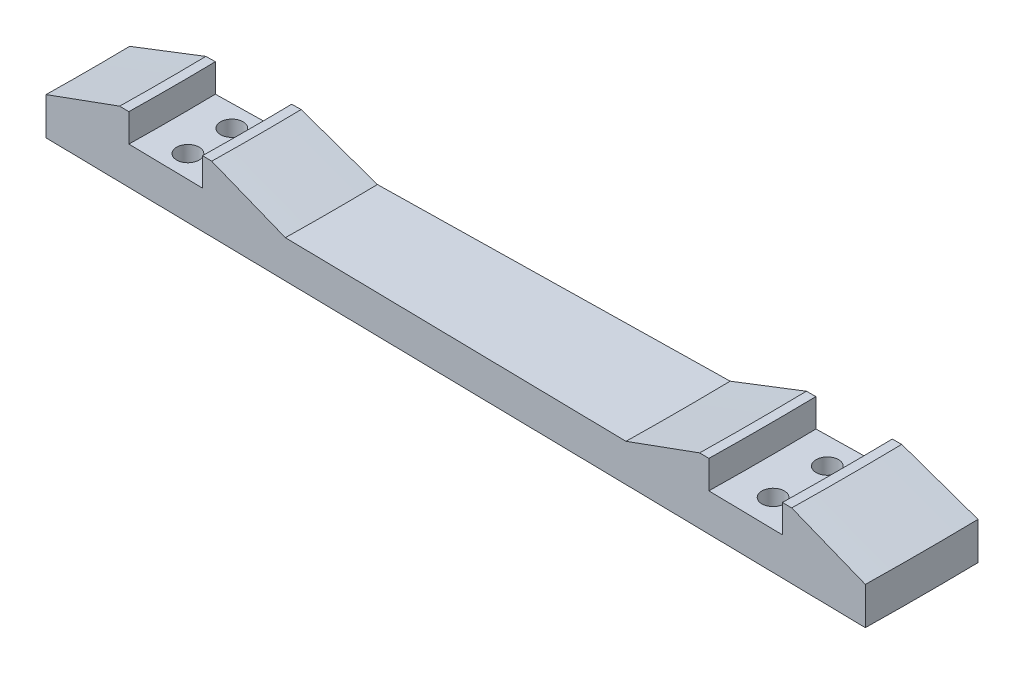
SolidWorks part; units mm, degrees
other "标注1"
sketch "草图3" plane through (-22.25, 4, -10) normal (-0.231, 0.6469, -0.7268) x (-0.9696, -0.2151, 0.1167)
ref_plane "前视基准面" through (0, 0, 0) normal (0, 0, 1) x (1, 0, 0)
ref_plane "上视基准面" through (0, 0, 0) normal (0, 1, 0) x (1, 0, 0)
ref_plane "右视基准面" through (0, 0, 0) normal (1, 0, 0) x (0, 0, -1)
other "Configuration Table"
sketch "草图4" plane through (0, 0, 0) normal (0, 0, 1) x (1, 0, 0)
  line L6 (8.5, -1.5) -> (17.75, -1.5)
  line L11 (17.75, -1.5) -> (17.75, -3.5)
  line L16 (17.75, -3.5) -> (-4.5, -3.5)
  line L17 (-4.5, -3.5) -> (-4.5, -1.5)
  line L19 (0, 0) -> (0, -1.5)
  line L20 (0, -1.5) -> (4, -1.5)
  line L21 (4, -1.5) -> (4, 0)
  line L26 (4, 0) -> (4.5, 0)
  line L27 (4.5, 0) -> (8.5, -1.5)
  line L28 (0, 0) -> (-0.5, 0)
  line L29 (-0.5, 0) -> (-4.5, -1.5)
  dimension "D2" = 4
  dimension "D4" = 0.5
  dimension "D5" = 2
  dimension "D6" = 2
  dimension "D7" = 4
  dimension "D8" = 1.5
  dimension "D9" = 4
  dimension "D10" = 22.25
extrude "凸台-拉伸1" add sketch "草图4" along normal blind 2.5 contours L28 L29 L17 L16 L11 L6 L27 L26 L21 L20 L19 | L19 | L21 region at (5.9579, -2.2764, 0)
sketch "草图5" plane through (0, -1.5, 0) normal (0, 1, 0) x (1, 0, 0)
  line L0 (0, 0) -> (4, -2.5) construction
  line L1 (0, -2.5) -> (0, 0) construction
  line L2 (0, -2.5) -> (4, -2.5) construction
  line L3 (4, -2.5) -> (4, 0) construction
  line L4 (0, 0) -> (4, 0) construction
  circle A0 centre (2, -1.25) radius 0.6
  circle A1 centre (2, -1.25) radius 1
  dimension "D1" = 1.2
  dimension "D2" = 2
extrude "切除-拉伸1" cut sketch "草图5" against normal through all contours A0
extrude "切除-拉伸2" cut sketch "草图5<3>" along normal blind 1 from surface contours A1 starting at face at (2, -3.5, 1.85)
sketch "草图5<3>" plane through (0, -1.5, 0) normal (0, 1, 0) x (1, 0, 0) same geometry as "草图5"
mirror "镜向1" about plane through (17.75, 0, 2.5) normal (1, 0, 0) of bodies 215
sketch "草图6" plane through (0, 0, 2.5) normal (0, 0, 1) x (1, 0, 0)
  line L18 (0, 0) -> (-0.5, 0)
  line L19 (-0.5, 0) -> (-4.5, -1.5)
  line L20 (-4.5, -1.5) -> (-4.5, -3.5)
  line L21 (-4.5, -3.5) -> (40, -3.5)
  line L22 (40, -3.5) -> (40, -1.5)
  line L23 (40, -1.5) -> (36, 0)
  line L24 (36, 0) -> (35.5, 0)
  line L25 (35.5, 0) -> (35.5, -1.5)
  line L26 (35.5, -1.5) -> (31.5, -1.5)
  line L27 (31.5, -1.5) -> (31.5, 0)
  line L28 (31.5, 0) -> (31, 0)
  line L29 (31, 0) -> (27, -1.5)
  line L30 (27, -1.5) -> (8.5, -1.5)
  line L31 (8.5, -1.5) -> (4.5, 0)
  line L32 (4.5, 0) -> (4, 0)
  line L33 (4, 0) -> (4, -1.5)
  line L34 (4, -1.5) -> (0, -1.5)
  line L35 (0, -1.5) -> (0, 0)
  line L36 (0, 0) -> (-0.5, 0)
  line L37 (-0.5, 0) -> (-4.5, -1.5)
  line L38 (-4.5, -1.5) -> (-4.5, -3.5)
  line L39 (-4.5, -3.5) -> (40, -3.5)
  line L40 (40, -3.5) -> (40, -1.5)
  line L41 (40, -1.5) -> (36, 0)
  line L42 (36, 0) -> (35.5, 0)
  line L43 (35.5, 0) -> (35.5, -1.5)
  line L44 (35.5, -1.5) -> (31.5, -1.5)
  line L45 (31.5, -1.5) -> (31.5, 0)
  line L46 (31.5, 0) -> (31, 0)
  line L47 (31, 0) -> (27, -1.5)
  line L48 (27, -1.5) -> (8.5, -1.5)
  line L49 (8.5, -1.5) -> (4.5, 0)
  line L50 (4.5, 0) -> (4, 0)
  line L51 (4, 0) -> (4, -1.5)
  line L52 (4, -1.5) -> (0, -1.5)
  line L53 (0, -1.5) -> (0, 0)
  dimension "D1" = 0
sketch "草图8" plane through (0, 0, 2.5) normal (0, 0, 1) x (1, 0, 0)
  line L0 (-132.25, 94.8536) -> (-132.25, -34.2886)
  line L1 (17.75, -1.5) -> (17.75, -3.5)
  line L2 (27, -1.5) -> (8.5, -1.5) construction
  line L3 (-4.5, -3.5) -> (40, -3.5) construction
  dimension "D1" = 150
revolve "旋转1" add sketch "草图6" angle 1 about L0
sketch "草图9" plane through (0, -1.5, 0) normal (0, 1, 0) x (1, 0, 0)
  line L0 (-0.005, -3.6541) -> (3.9948, -3.689) construction
  line L1 (3.9948, -3.689) -> (31.4938, -3.929) construction
  line L2 (31.4938, -3.929) -> (35.4936, -3.9639) construction
  arc A0 (-0.0201, -4.8081) -> (0, -2.5) centre (-132.25, -2.5) ccw construction
  arc A1 (3.9792, -4.8779) -> (4, -2.5) centre (-132.25, -2.5) ccw construction
  arc A2 (31.4751, -5.3578) -> (31.5, -2.5) centre (-132.25, -2.5) ccw construction
  arc A3 (35.4745, -5.4276) -> (35.5, -2.5) centre (-132.25, -2.5) ccw construction
  circle A4 centre (1.9949, -3.6715) radius 1
  circle A5 centre (1.9949, -3.6715) radius 0.6
  circle A6 centre (33.4937, -3.9464) radius 1
  circle A7 centre (33.4937, -3.9464) radius 0.6
  dimension "D1" = 2
  dimension "D2" = 1.2
extrude "切除-拉伸3" cut sketch "草图9" against normal through all contours A7 | A5
extrude "切除-拉伸4" cut sketch "草图9<3>" along normal blind 1 from surface contours A6 | A4 starting at face at (32.8937, -3.5, 3.9464)
sketch "草图9<3>" plane through (0, -1.5, 0) normal (0, 1, 0) x (1, 0, 0) same geometry as "草图9"
sketch "草图10" plane through (0, 0, 0) normal (0, 1, 0) x (1, 0, 0)
  line L1 (40, -2.5) -> (-4.5, -2.5)
  line L2 (40, -2.5) -> (40, 0)
  line L3 (40, 0) -> (-4.5, 0)
  line L4 (-4.5, -2.5) -> (-4.5, 0)
extrude "切除-拉伸5" cut sketch "草图10" against normal through all
mirror "镜向2" about plane through (40, -3.5, 2.5) normal (0, 0, 1) of bodies 220
sketch "草图11" plane through (0, -1.5, 0) normal (0, 1, 0) x (1, 0, 0)
  line L0 (8.5, -2.5) -> (12.2503, -2.5) construction
  line L1 (10.9975, -3.3822) -> (10.7479, -1.6222)
  line L2 (10.7479, -1.6222) -> (13.7471, -1.5698)
  line L3 (13.7471, -1.5698) -> (13.4975, -3.4258)
  line L4 (-4.5, -2.5) -> (-0.5, -2.5) construction
  line L5 (10.9975, -3.3822) -> (8.4975, -3.3386)
  line L6 (13.4975, -3.4258) -> (16.4967, -3.4782)
  line L7 (16.4967, -3.4782) -> (16.2471, -1.5262)
  line L8 (16.2471, -1.5262) -> (19.2462, -1.4738)
  line L9 (19.2462, -1.4738) -> (18.9967, -3.5218)
  line L10 (16.4967, -3.4782) -> (18.9967, -3.5218) construction
  line L11 (12.2503, -2.5) -> (17.75, -2.5) construction
  line L12 (18.9967, -3.5218) -> (21.9958, -3.5742)
  line L13 (21.9958, -3.5742) -> (21.7462, -1.4302)
  line L14 (21.7462, -1.4302) -> (26.9958, -1.3386)
  line L15 (26.9757, 0.2793) -> (8.4786, -0.0436) construction
  line L16 (10.9975, -3.3822) -> (13.4975, -3.4258) construction
  line L17 (21.9958, -3.5742) -> (26.9958, -3.6614) construction
  line L18 (26.9757, -5.2793) -> (8.4786, -4.9564) construction
  line L19 (13.7471, -1.5698) -> (16.2471, -1.5262) construction
  line L20 (19.2462, -1.4738) -> (21.7462, -1.4302) construction
  arc A0 (8.4786, -4.9564) -> (8.4786, -0.0436) centre (-132.25, -2.5) ccw construction
  arc A1 (-4.5195, -4.7295) -> (-4.5195, -0.2705) centre (-132.25, -2.5) ccw construction
  arc A2 (-0.5201, -4.7994) -> (-0.5201, -0.2006) centre (-132.25, -2.5) ccw construction
  arc A3 (17.7467, -1.5) -> (17.7467, -3.5) centre (-132.25, -2.5) cw construction
  arc A4 (12.2475, -1.596) -> (12.2475, -3.404) centre (-132.25, -2.5) cw construction
  arc A5 (26.9757, -5.2793) -> (26.9757, 0.2793) centre (-132.25, -2.5) ccw construction
  arc A7 (17.7272, 0.1179) -> (17.7272, -5.1179) centre (-132.25, -2.5) cw
  point P27 (22.7312, -3.5218)
  dimension "D1" = 2
  dimension "D2" = 2.5
